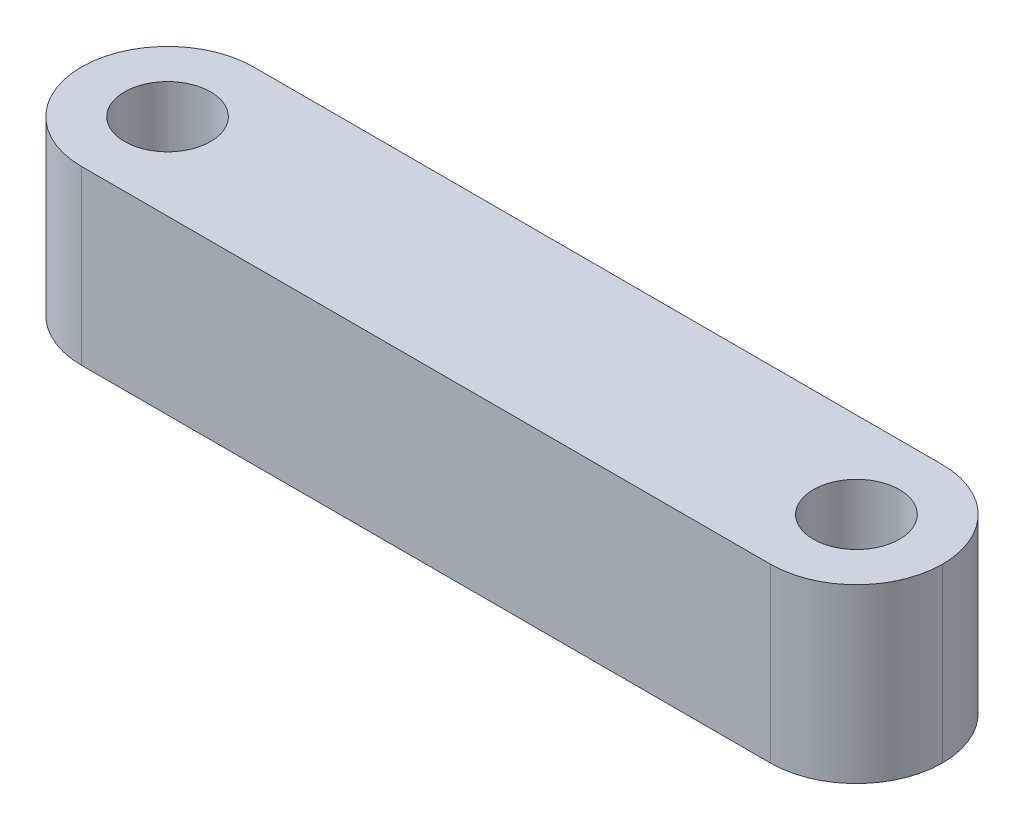
SolidWorks part; units mm, degrees
ref_plane "Front" through (0, 0, 0) normal (0, 0, 1) x (1, 0, 0)
ref_plane "Top" through (0, 0, 0) normal (0, 1, 0) x (1, 0, 0)
ref_plane "Right" through (0, 0, 0) normal (1, 0, 0) x (0, 0, -1)
sketch "Sketch1" plane through (0, 0, 0) normal (0, 1, 0) x (1, 0, 0)
  line L1 (-12.5, -2.5) -> (12.5, -2.5)
  line L2 (-12.5, -2.5) -> (-12.5, 2.5)
  line L3 (-12.5, 2.5) -> (12.5, 2.5)
  line L4 (12.5, -2.5) -> (12.5, 2.5)
  line L5 (-12.5, -2.5) -> (12.5, 2.5) construction
  line L6 (-12.5, 2.5) -> (12.5, -2.5) construction
  point P0 (0, 0)
  dimension "D1" = 25
  dimension "D2" = 5
extrude "Boss-Extrude1" add sketch "Sketch1" along normal blind 5
sketch "Sketch2" plane through (0, 5, 0) normal (0, 1, 0) x (1, 0, 0)
  line L0 (-12.5, 2.5) -> (-12.5, -2.5) construction
  line L1 (12.5, -2.5) -> (12.5, 2.5) construction
  circle A0 centre (-10, 0) radius 1.25
  circle A1 centre (10, 0) radius 1.25
  dimension "D1" = 2.5
  dimension "D2" = 2.5
  dimension "D3" = 2.5
extrude "Cut-Extrude1" cut sketch "Sketch2" against normal through all
fillet "Fillet1" radius 2.5 4 edges at (12.5, 2.5, 2.5) (12.5, 2.5, -2.5) (-12.5, 2.5, 2.5) (-12.5, 2.5, -2.5)
